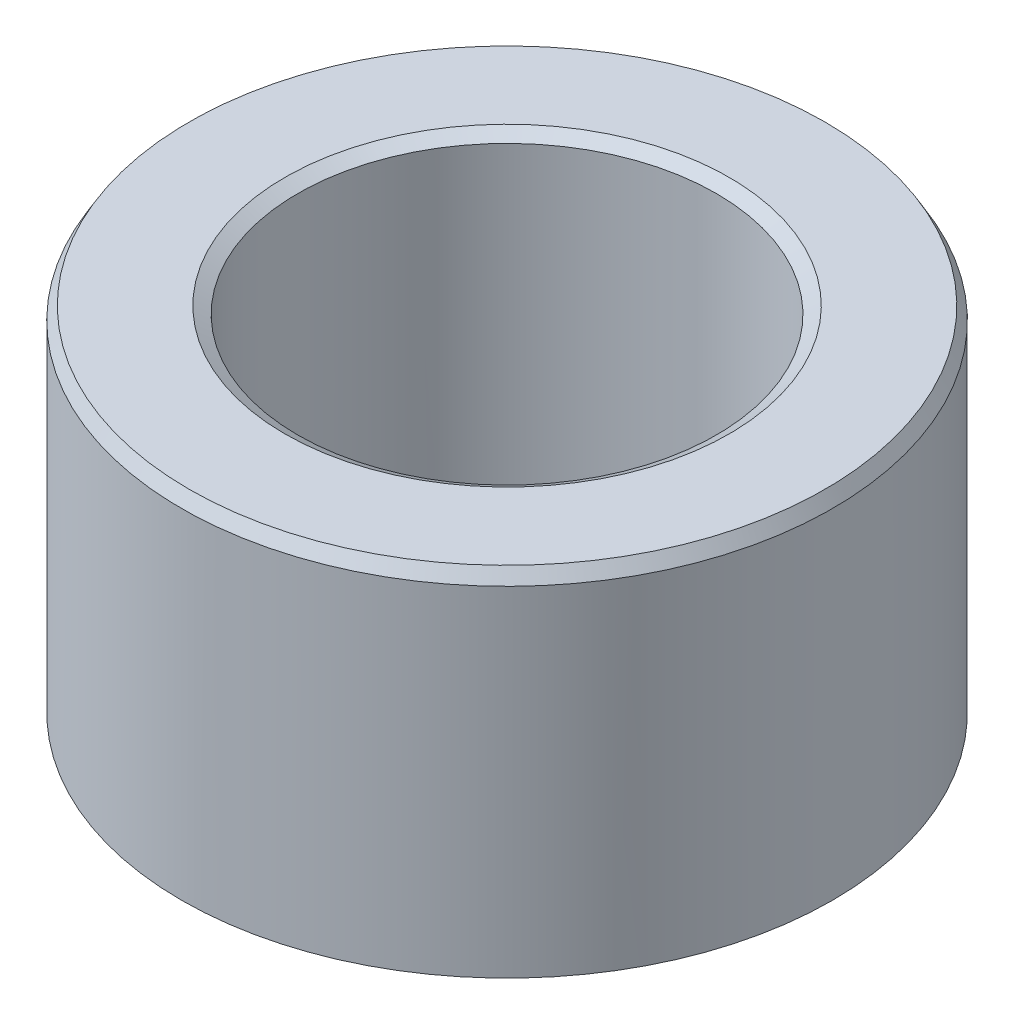
SolidWorks part; units mm, degrees
ref_plane "Front Plane" through (0, 0, 0) normal (0, 0, 1) x (1, 0, 0)
ref_plane "Top Plane" through (0, 0, 0) normal (0, 1, 0) x (1, 0, 0)
ref_plane "Right Plane" through (0, 0, 0) normal (1, 0, 0) x (0, 0, -1)
sketch "Sketch1" plane through (0, 0, 0) normal (0, 1, 0) x (1, 0, 0)
  circle A0 centre (0, 0) radius 30
  dimension "SLEEVE_OD" = 60
extrude "Boss-Extrude1" add sketch "Sketch1" along normal blind 33.1529
sketch "Sketch2" plane through (0, 0, 0) normal (0, 1, 0) x (1, 0, 0)
  circle A0 centre (0, 0) radius 19.2862
  dimension "BORE_D" = 38.5723
extrude "Cut-Extrude1" cut sketch "Sketch2" along normal through all
chamfer "Chamfer1" distance 1.1923 angle 30 4 edges at (0, 33.1529, 19.2862) (0, 0, 19.2862) (0, 0, 30) (0, 33.1529, 30) first distance on face at (0, 33.1529, 19.2862) first distance on face at (0, 0, 19.2862) first distance on face at (0, 33.1529, 30)
